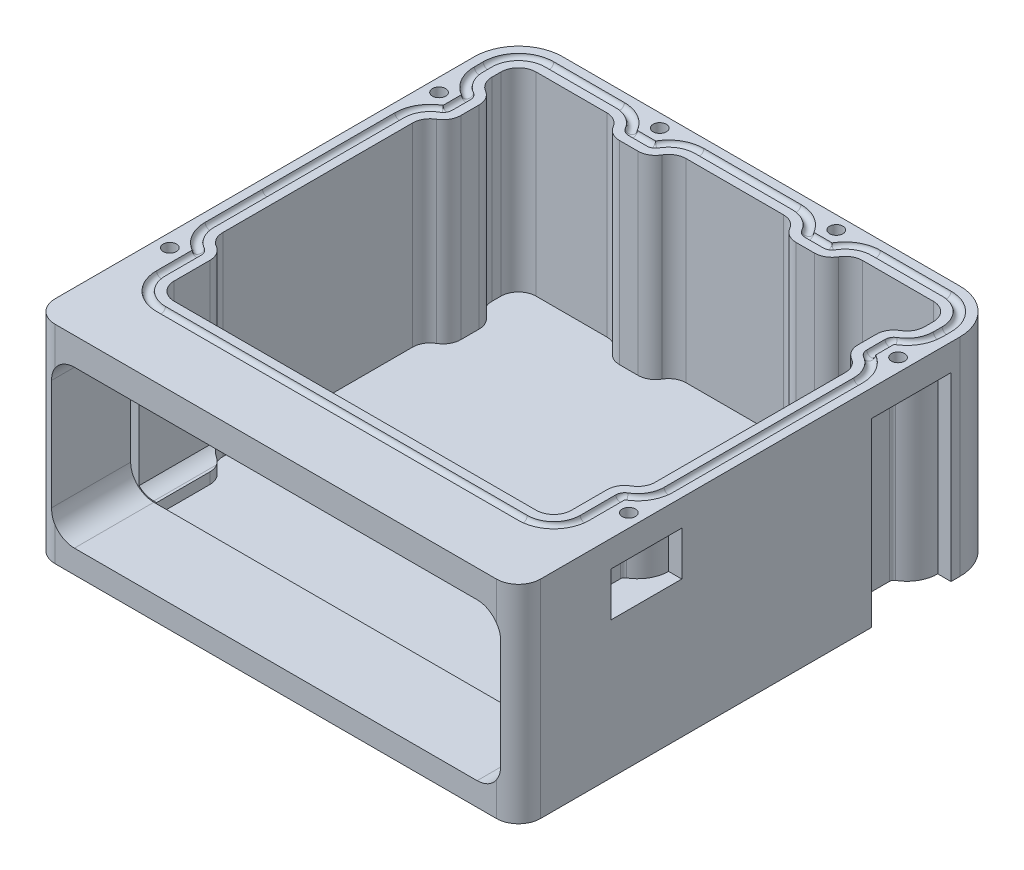
SolidWorks part; units mm, degrees
ref_plane "Front Plane" through (0, 0, 0) normal (0, 0, 1) x (1, 0, 0)
ref_plane "Top Plane" through (0, 0, 0) normal (0, 1, 0) x (1, 0, 0)
ref_plane "Right Plane" through (0, 0, 0) normal (1, 0, 0) x (0, 0, -1)
sketch "Sketch1" plane through (0, 0, 0) normal (0, 1, 0) x (1, 0, 0)
  line L1 (-45, 220) -> (45, 220)
  line L2 (-55, 210) -> (-55, 115)
  line L3 (-50, 110) -> (50, 110)
  line L4 (55, 210) -> (55, 115)
  arc A0 (45, 220) -> (55, 210) centre (45, 210) cw
  arc A1 (-45, 220) -> (-55, 210) centre (-45, 210) ccw
  arc A2 (50, 110) -> (55, 115) centre (50, 115) ccw
  arc A3 (-55, 115) -> (-50, 110) centre (-50, 115) ccw
  point P9 (-55, 220)
  point P12 (55, 110)
  point P15 (-55, 110)
  dimension "D5" = 10
  dimension "D6" = 5
  dimension "D1" = 110
  dimension "D2" = 110
  dimension "D3" = 55
  dimension "D4" = 110
extrude "Extrude-Thin1" add sketch "Sketch1" along normal blind 20 and the other way blind 27 thin thin type one direction reverse wall 6
sketch "Sketch2" plane through (0, -27, 0) normal (0, -1, 0) x (1, 0, 0)
  line L5 (-49, -116) -> (49, -116)
  line L6 (49, -116) -> (49, -210)
  line L7 (-49, -116) -> (-49, -210)
  line L8 (-45, -214) -> (45, -214)
  arc A6 (45, -214) -> (49, -210) centre (45, -210) ccw
  arc A7 (-49, -210) -> (-45, -214) centre (-45, -210) ccw
extrude "Boss-Extrude1" add sketch "Sketch2" against normal blind 3 contours A7 L8 A6 L6 L5 L7
sketch "Sketch4" plane through (0, 0, -116) normal (0, 0, -1) x (-1, 0, 0)
  line L0 (-45, 20) -> (-55, 20) construction
  line L1 (-52, 20) -> (52, 20)
  line L2 (-52, 20) -> (-52, -27)
  line L3 (-52, -27) -> (52, -27)
  line L4 (52, 20) -> (52, -27)
  line L5 (45, -27) -> (55, -27) construction
  line L6 (-55, -27) -> (-55, 20) construction
  line L7 (55, -27) -> (55, 20) construction
  dimension "D1" = 3
  dimension "D2" = 3
extrude "Boss-Extrude2" add sketch "Sketch4" along normal blind 12
sketch "Sketch3" plane through (0, 0, -110) normal (0, 0, 1) x (1, 0, 0)
  line L0 (-45.625, 13.75) -> (45.625, 13.75)
  line L5 (50.875, 8.5) -> (50.875, -16.5)
  line L6 (-45.625, 13.5) -> (45.625, 13.5)
  line L7 (-50.625, 8.5) -> (-50.625, -16.5)
  line L8 (-45.625, -21.5) -> (45.625, -21.5)
  line L9 (50.625, 8.5) -> (50.625, -16.5)
  line L10 (-45.625, -21.75) -> (45.625, -21.75)
  line L11 (-50.875, 8.5) -> (-50.875, -16.5)
  arc A1 (45.625, 13.75) -> (50.875, 8.5) centre (45.625, 8.5) cw
  arc A5 (-50.625, -16.5) -> (-45.625, -21.5) centre (-45.625, -16.5) ccw
  arc A6 (45.625, -21.5) -> (50.625, -16.5) centre (45.625, -16.5) ccw
  arc A7 (45.625, 13.5) -> (50.625, 8.5) centre (45.625, 8.5) cw
  arc A8 (-45.625, 13.5) -> (-50.625, 8.5) centre (-45.625, 8.5) ccw
  arc A9 (45.625, -21.75) -> (50.875, -16.5) centre (45.625, -16.5) ccw
  arc A10 (-50.875, -16.5) -> (-45.625, -21.75) centre (-45.625, -16.5) ccw
  arc A11 (-45.625, 13.75) -> (-50.875, 8.5) centre (-45.625, 8.5) ccw
  dimension "D1" = 5
  dimension "D5" = 13.5
  dimension "D2" = 50.625
  dimension "D3" = 101.25
  dimension "D4" = 35
  dimension "D6" = 0.25
extrude "Cut-Extrude1" cut sketch "Sketch3" against normal blind 18 contours L0 A1 L5 A9 L10 A10 L11 A11
sketch "Sketch5" plane through (0, -24, 0) normal (0, 1, 0) x (1, 0, 0)
  line L0 (0, 220) -> (0, 110) construction
  line L1 (45, 220) -> (-45, 220) construction
  line L2 (-50, 110) -> (50, 110) construction
  line L3 (45, 214) -> (-45, 214) construction
  line L4 (-15, 214) -> (-25, 214)
  line L5 (-15, 214) -> (-15, 210)
  line L6 (-15, 210) -> (-25, 210)
  line L7 (-25, 214) -> (-25, 210)
  line L8 (-45, 220) -> (-45, 188) construction
  line L9 (15, 214) -> (25, 214)
  line L10 (15, 214) -> (15, 210)
  line L11 (15, 210) -> (25, 210)
  line L12 (25, 214) -> (25, 210)
  line L13 (-45, 188) -> (-45, 210) construction
  line L14 (-45, 210) -> (-55, 210) construction
  line L15 (-55, 210) -> (55, 210) construction
  line L16 (45, 220) -> (45, 162.7672) construction
  line L17 (-49, 210) -> (-49, 128) construction
  line L18 (-45, 204) -> (-49, 204)
  line L19 (-45, 204) -> (-45, 194)
  line L20 (-45, 194) -> (-49, 194)
  line L21 (-49, 204) -> (-49, 194)
  line L22 (49, 128) -> (49, 210) construction
  line L23 (45, 204) -> (49, 204)
  line L24 (45, 204) -> (45, 194)
  line L25 (45, 194) -> (49, 194)
  line L26 (49, 204) -> (49, 194)
  line L27 (-49, 210) -> (-49, 128)
  line L28 (-49, 128) -> (-45, 128)
  line L29 (-49, 128) -> (-49, 143)
  line L30 (-49, 143) -> (-45, 143)
  line L31 (-45, 128) -> (-45, 143)
  line L32 (49, 128) -> (45, 128)
  line L33 (49, 128) -> (49, 143)
  line L34 (49, 143) -> (45, 143)
  line L35 (45, 128) -> (45, 143)
  line L36 (-45, 214) -> (45, 214)
  line L37 (49, 210) -> (49, 128)
  line M1 (-49, 210) -> (-49, 128)
  line M2 (-49, 128) -> (49, 128)
  line M6 (-49, 128) -> (49, 128)
  line M7 (49, 128) -> (49, 210)
  line M9 (45, 214) -> (-45, 214)
  dimension "D1" = 6
  dimension "D2" = 6
  dimension "D3" = 20
  dimension "D4" = 20
  dimension "D5" = 10
  dimension "D6" = 10
  dimension "D7" = 10
  dimension "D8" = 10
  dimension "D9" = 15
  dimension "D10" = 15
  dimension "D11" = 4
  dimension "D12" = 4
  dimension "D13" = 4
  dimension "D14" = 4
extrude "Boss-Extrude3" add sketch "Sketch5" along normal up to surface (44 mm away) contours L35 L34 M6 M7 | L24 L25 L23 M7 | L12 L10 L11 M9 | L7 L6 L5 M9 | L20 L19 L18 M1 | L31 L30 L27 M2 region at (-20, -24, -212) region at (20, -24, -212) region at (-47, -24, -199) region at (47, -24, -199) region at (47, -24, -135.5) region at (-47, -24, -135.5) up to face at (0, 20, -184.2761)
fillet "Fillet1" radius 4 10 edges at (49, -2, -194) (49, -2, -204) (25, -2, -214) (15, -2, -214) (-15, -2, -214) (-25, -2, -214) (-49, -2, -204) (-49, -2, -194) (49, -2, -143) (-49, -2, -143)
fillet "Fillet2" radius 4 12 edges at (-45, 16.875, -128) (45, 16.875, -128) (45, -2, -143) (-45, -2, -143) (45, -2, -204) (45, -2, -194) (25, -2, -210) (15, -2, -210) (-15, -2, -210) (-25, -2, -210) (-45, -2, -204) (-45, -2, -194)
ref_plane "Plane1" through (0, 0, -160) normal (0, 0, 1) x (1, 0, 0)
sketch "Sketch9" plane through (0, 20, 0) normal (0, 1, 0) x (1, 0, 0)
  line L329 (-17.9282, 213) -> (-22.0718, 213)
  line L330 (11, 217) -> (-11, 217)
  line L331 (22.0718, 213) -> (17.9282, 213)
  line L332 (45, 217) -> (29, 217)
  line L333 (52, 208) -> (52, 210)
  line L334 (48, 196.9282) -> (48, 201.0718)
  line L335 (52, 147) -> (52, 190)
  line L336 (48, 132) -> (48, 140.0718)
  line L337 (-41, 125) -> (41, 125)
  line L338 (-48, 140.0718) -> (-48, 132)
  line L339 (-52, 190) -> (-52, 147)
  line L340 (-48, 201.0718) -> (-48, 196.9282)
  line L341 (-52, 210) -> (-52, 208)
  line L342 (-29, 217) -> (-45, 217)
  line L343 (-17.9282, 213) -> (-22.0718, 213)
  line L344 (11, 217) -> (-11, 217)
  line L345 (22.0718, 213) -> (17.9282, 213)
  line L346 (45, 217) -> (29, 217)
  line L347 (52, 208) -> (52, 210)
  line L348 (48, 196.9282) -> (48, 201.0718)
  line L349 (52, 147) -> (52, 190)
  line L350 (48, 132) -> (48, 140.0718)
  line L351 (-41, 125) -> (41, 125)
  line L352 (-48, 140.0718) -> (-48, 132)
  line L353 (-52, 190) -> (-52, 147)
  line L354 (-48, 201.0718) -> (-48, 196.9282)
  line L355 (-52, 210) -> (-52, 208)
  line L356 (-29, 217) -> (-45, 217)
  arc A534 (-22.9378, 213.5) -> (-29, 217) centre (-29, 210) ccw
  arc A535 (-22.9378, 213.5) -> (-22.0718, 213) centre (-22.0718, 214) ccw
  arc A536 (-17.9282, 213) -> (-17.0622, 213.5) centre (-17.9282, 214) ccw
  arc A537 (-11, 217) -> (-17.0622, 213.5) centre (-11, 210) ccw
  arc A538 (17.0622, 213.5) -> (11, 217) centre (11, 210) ccw
  arc A539 (17.0622, 213.5) -> (17.9282, 213) centre (17.9282, 214) ccw
  arc A540 (22.0718, 213) -> (22.9378, 213.5) centre (22.0718, 214) ccw
  arc A541 (29, 217) -> (22.9378, 213.5) centre (29, 210) ccw
  arc A542 (52, 210) -> (45, 217) centre (45, 210) ccw
  arc A543 (48.5, 201.9378) -> (52, 208) centre (45, 208) ccw
  arc A544 (48.5, 201.9378) -> (48, 201.0718) centre (49, 201.0718) ccw
  arc A545 (48, 196.9282) -> (48.5, 196.0622) centre (49, 196.9282) ccw
  arc A546 (52, 190) -> (48.5, 196.0622) centre (45, 190) ccw
  arc A547 (48.5, 140.9378) -> (52, 147) centre (45, 147) ccw
  arc A548 (48.5, 140.9378) -> (48, 140.0718) centre (49, 140.0718) ccw
  arc A549 (41, 125) -> (48, 132) centre (41, 132) ccw
  arc A550 (-48, 132) -> (-41, 125) centre (-41, 132) ccw
  arc A551 (-48, 140.0718) -> (-48.5, 140.9378) centre (-49, 140.0718) ccw
  arc A552 (-52, 147) -> (-48.5, 140.9378) centre (-45, 147) ccw
  arc A553 (-48.5, 196.0622) -> (-52, 190) centre (-45, 190) ccw
  arc A554 (-48.5, 196.0622) -> (-48, 196.9282) centre (-49, 196.9282) ccw
  arc A555 (-48, 201.0718) -> (-48.5, 201.9378) centre (-49, 201.0718) ccw
  arc A556 (-52, 208) -> (-48.5, 201.9378) centre (-45, 208) ccw
  arc A557 (-45, 217) -> (-52, 210) centre (-45, 210) ccw
  arc A558 (-22.9378, 213.5) -> (-29, 217) centre (-29, 210) ccw
  arc A559 (-22.9378, 213.5) -> (-22.0718, 213) centre (-22.0718, 214) ccw
  arc A560 (-17.9282, 213) -> (-17.0622, 213.5) centre (-17.9282, 214) ccw
  arc A561 (-11, 217) -> (-17.0622, 213.5) centre (-11, 210) ccw
  arc A562 (17.0622, 213.5) -> (11, 217) centre (11, 210) ccw
  arc A563 (17.0622, 213.5) -> (17.9282, 213) centre (17.9282, 214) ccw
  arc A564 (22.0718, 213) -> (22.9378, 213.5) centre (22.0718, 214) ccw
  arc A565 (29, 217) -> (22.9378, 213.5) centre (29, 210) ccw
  arc A566 (52, 210) -> (45, 217) centre (45, 210) ccw
  arc A567 (48.5, 201.9378) -> (52, 208) centre (45, 208) ccw
  arc A568 (48.5, 201.9378) -> (48, 201.0718) centre (49, 201.0718) ccw
  arc A569 (48, 196.9282) -> (48.5, 196.0622) centre (49, 196.9282) ccw
  arc A570 (52, 190) -> (48.5, 196.0622) centre (45, 190) ccw
  arc A571 (48.5, 140.9378) -> (52, 147) centre (45, 147) ccw
  arc A572 (48.5, 140.9378) -> (48, 140.0718) centre (49, 140.0718) ccw
  arc A573 (41, 125) -> (48, 132) centre (41, 132) ccw
  arc A574 (-48, 132) -> (-41, 125) centre (-41, 132) ccw
  arc A575 (-48, 140.0718) -> (-48.5, 140.9378) centre (-49, 140.0718) ccw
  arc A576 (-52, 147) -> (-48.5, 140.9378) centre (-45, 147) ccw
  arc A577 (-48.5, 196.0622) -> (-52, 190) centre (-45, 190) ccw
  arc A578 (-48.5, 196.0622) -> (-48, 196.9282) centre (-49, 196.9282) ccw
  arc A579 (-48, 201.0718) -> (-48.5, 201.9378) centre (-49, 201.0718) ccw
  arc A580 (-52, 208) -> (-48.5, 201.9378) centre (-45, 208) ccw
  arc A581 (-45, 217) -> (-52, 210) centre (-45, 210) ccw
  dimension "D1" = 3
sketch "Sketch6" plane through (0, 0, -160) normal (0, 0, 1) x (1, 0, 0)
  line L0 (-45, 20) -> (-52, 20) construction
  line L1 (-50, 20) -> (-55, 20) construction
  circle A0 centre (-52, 20) radius 1
  dimension "D1" = 2
  dimension "D2" = 3
ref_plane "Plane2" through (0, 14, 0) normal (0, 1, 0) x (1, 0, 0)
sketch "Sketch10" plane through (0, 14, 0) normal (0, 1, 0) x (1, 0, 0)
  line L0 (-52, 147) -> (-55, 147)
  line L2 (52, 208) -> (55, 208)
  line L3 (-29, 220) -> (-29, 217)
  line L6 (-17.9282, 213) -> (-22.0718, 213)
  line L9 (-17.9282, 213) -> (-22.0718, 213)
  line L10 (-11, 217) -> (-11, 220)
  line L11 (-52, 208) -> (-55, 208)
  line L14 (-48, 201.0718) -> (-48, 196.9282)
  line L15 (-48, 201.0718) -> (-48, 196.9282)
  line L16 (-55, 190) -> (-52, 190)
  line L18 (48, 196.9282) -> (48, 201.0718)
  line L21 (48, 196.9282) -> (48, 201.0718)
  line L25 (-55, 210) -> (-55, 115) construction
  line L26 (-55, 208) -> (-55, 190)
  line L29 (45, 220) -> (-45, 220) construction
  line L30 (-29, 220) -> (-11, 220)
  line L33 (11, 220) -> (29, 220)
  line L36 (55, 115) -> (55, 210) construction
  line L37 (55, 208) -> (55, 190)
  line L40 (-55, 131) -> (-50.5, 131)
  line L41 (-48, 133.5) -> (-48, 140.0718)
  line L47 (52, 190) -> (55, 190)
  line L48 (-50, 110) -> (50, 110) construction
  line L49 (-55, 147) -> (-55, 131)
  line L50 (48, 140.0718) -> (48, 133.5)
  line L51 (50.5, 131) -> (55, 131)
  line L52 (-48, 140.0718) -> (-48, 132)
  line L55 (29, 217) -> (29, 220)
  line L56 (22.0718, 213) -> (17.9282, 213)
  line L57 (22.0718, 213) -> (17.9282, 213)
  line L58 (11, 220) -> (11, 217)
  line L59 (55, 131) -> (55, 147)
  line L60 (55, 147) -> (52, 147)
  line L61 (48, 132) -> (48, 140.0718)
  arc A0 (-50.5, 131) -> (-48, 133.5) centre (-50.5, 133.5) ccw
  arc A1 (48, 133.5) -> (50.5, 131) centre (50.5, 133.5) ccw
  arc A11 (52, 190) -> (48.5, 196.0622) centre (45, 190) ccw
  arc A12 (48, 196.9282) -> (48.5, 196.0622) centre (49, 196.9282) ccw
  arc A13 (-11, 217) -> (-17.0622, 213.5) centre (-11, 210) ccw
  arc A18 (-17.9282, 213) -> (-17.0622, 213.5) centre (-17.9282, 214) ccw
  arc A19 (-22.9378, 213.5) -> (-22.0718, 213) centre (-22.0718, 214) ccw
  arc A20 (48.5, 201.9378) -> (48, 201.0718) centre (49, 201.0718) ccw
  arc A21 (48.5, 201.9378) -> (52, 208) centre (45, 208) ccw
  arc A26 (-48.5, 196.0622) -> (-52, 190) centre (-45, 190) ccw
  arc A27 (-48.5, 196.0622) -> (-48, 196.9282) centre (-49, 196.9282) ccw
  arc A28 (-48, 201.0718) -> (-48.5, 201.9378) centre (-49, 201.0718) ccw
  arc A29 (-52, 208) -> (-48.5, 201.9378) centre (-45, 208) ccw
  arc A30 (-48.5, 196.0622) -> (-52, 190) centre (-45, 190) ccw
  arc A31 (-48.5, 196.0622) -> (-48, 196.9282) centre (-49, 196.9282) ccw
  arc A32 (-48, 201.0718) -> (-48.5, 201.9378) centre (-49, 201.0718) ccw
  arc A33 (-52, 208) -> (-48.5, 201.9378) centre (-45, 208) ccw
  arc A34 (52, 190) -> (48.5, 196.0622) centre (45, 190) ccw
  arc A35 (48, 196.9282) -> (48.5, 196.0622) centre (49, 196.9282) ccw
  arc A36 (48.5, 201.9378) -> (48, 201.0718) centre (49, 201.0718) ccw
  arc A37 (-22.9378, 213.5) -> (-29, 217) centre (-29, 210) ccw
  arc A38 (-11, 217) -> (-17.0622, 213.5) centre (-11, 210) ccw
  arc A39 (-17.9282, 213) -> (-17.0622, 213.5) centre (-17.9282, 214) ccw
  arc A40 (-22.9378, 213.5) -> (-22.0718, 213) centre (-22.0718, 214) ccw
  arc A41 (-22.9378, 213.5) -> (-29, 217) centre (-29, 210) ccw
  arc A42 (48.5, 201.9378) -> (52, 208) centre (45, 208) ccw
  arc A61 (-48, 140.0718) -> (-48.5, 140.9378) centre (-49, 140.0718) ccw
  arc A62 (-52, 147) -> (-48.5, 140.9378) centre (-45, 147) ccw
  arc A63 (-48, 140.0718) -> (-48.5, 140.9378) centre (-49, 140.0718) ccw
  arc A64 (-52, 147) -> (-48.5, 140.9378) centre (-45, 147) ccw
  arc A73 (48.5, 140.9378) -> (48, 140.0718) centre (49, 140.0718) ccw
  arc A78 (29, 217) -> (22.9378, 213.5) centre (29, 210) ccw
  arc A79 (22.0718, 213) -> (22.9378, 213.5) centre (22.0718, 214) ccw
  arc A80 (17.0622, 213.5) -> (17.9282, 213) centre (17.9282, 214) ccw
  arc A81 (17.0622, 213.5) -> (11, 217) centre (11, 210) ccw
  arc A82 (29, 217) -> (22.9378, 213.5) centre (29, 210) ccw
  arc A83 (22.0718, 213) -> (22.9378, 213.5) centre (22.0718, 214) ccw
  arc A84 (17.0622, 213.5) -> (17.9282, 213) centre (17.9282, 214) ccw
  arc A85 (17.0622, 213.5) -> (11, 217) centre (11, 210) ccw
  arc A90 (48.5, 140.9378) -> (52, 147) centre (45, 147) ccw
  arc A91 (48.5, 140.9378) -> (48, 140.0718) centre (49, 140.0718) ccw
  arc A92 (48.5, 140.9378) -> (52, 147) centre (45, 147) ccw
  dimension "D8" = 21
  dimension "D9" = 2.5
  dimension "D11" = 2.5
  dimension "D10" = 21
  dimension "D1" = 3
  dimension "D2" = 3
  dimension "D3" = 3
  dimension "D4" = 3
  dimension "D5" = 3
  dimension "D7" = 3
extrude "Cut-Extrude2" cut sketch "Sketch10" against normal blind 10
sketch "Sketch11" plane through (0, 14, 0) normal (0, -1, 0) x (1, 0, 0)
  line L0 (-55, -210) -> (-55, -115) construction
  line L1 (45, -220) -> (-45, -220) construction
  line L2 (55, -115) -> (55, -210) construction
  circle A0 centre (-52, -199) radius 1.5
  circle A1 centre (-20, -217.003) radius 1.5
  circle A2 centre (20, -217.003) radius 1.5
  circle A3 centre (52, -199) radius 1.5
  circle A4 centre (52, -138) radius 1.5
  circle A5 centre (-52, -138) radius 1.5
  point P7 (-49, -190)
  dimension "D3" = 3
  dimension "D4" = 3
  dimension "D5" = 3
  dimension "D6" = 3
  dimension "D8" = 2.997
  dimension "D9" = 9
  dimension "D10" = 2.997
  dimension "D11" = 9
  dimension "D12" = 3
  dimension "D13" = 3
  dimension "D14" = 3
  dimension "D17" = 3
  dimension "D18" = 3
  dimension "D2" = 9
  dimension "D7" = 9
  dimension "D15" = 9
  dimension "D16" = 9
  dimension "D1" = 3
extrude "Cut-Extrude3" cut sketch "Sketch11" against normal through all
sketch "Sketch15" plane through (0, 4, 0) normal (0, 1, 0) x (1, 0, 0)
  line L8 (-55, 208) -> (-55, 190)
  line L9 (-55, 190) -> (-52, 190)
  line L10 (-48, 196.9282) -> (-48, 201.0718)
  line L11 (-52, 208) -> (-55, 208)
  line L12 (-55, 208) -> (-55, 190)
  line L13 (-55, 190) -> (-52, 190)
  line L14 (-48, 196.9282) -> (-48, 201.0718)
  line L15 (-52, 208) -> (-55, 208)
  line L20 (-11, 220) -> (-29, 220)
  line L21 (-29, 220) -> (-29, 217)
  line L22 (-22.0718, 213) -> (-17.9282, 213)
  line L23 (-11, 217) -> (-11, 220)
  line L24 (-11, 220) -> (-29, 220)
  line L25 (-29, 220) -> (-29, 217)
  line L26 (-22.0718, 213) -> (-17.9282, 213)
  line L27 (-11, 217) -> (-11, 220)
  line L32 (29, 217) -> (29, 220)
  line L33 (29, 220) -> (11, 220)
  line L34 (11, 220) -> (11, 217)
  line L35 (17.9282, 213) -> (22.0718, 213)
  line L36 (29, 217) -> (29, 220)
  line L37 (29, 220) -> (11, 220)
  line L38 (11, 220) -> (11, 217)
  line L39 (17.9282, 213) -> (22.0718, 213)
  line L44 (55, 190) -> (55, 208)
  line L45 (55, 208) -> (52, 208)
  line L46 (48, 201.0718) -> (48, 196.9282)
  line L47 (52, 190) -> (55, 190)
  line L48 (55, 190) -> (55, 208)
  line L49 (55, 208) -> (52, 208)
  line L50 (48, 201.0718) -> (48, 196.9282)
  line L51 (52, 190) -> (55, 190)
  arc A8 (-48.5, 196.0622) -> (-52, 190) centre (-45, 190) ccw
  arc A9 (-48.5, 196.0622) -> (-48, 196.9282) centre (-49, 196.9282) ccw
  arc A10 (-48, 201.0718) -> (-48.5, 201.9378) centre (-49, 201.0718) ccw
  arc A11 (-52, 208) -> (-48.5, 201.9378) centre (-45, 208) ccw
  arc A12 (-48.5, 196.0622) -> (-52, 190) centre (-45, 190) ccw
  arc A13 (-48.5, 196.0622) -> (-48, 196.9282) centre (-49, 196.9282) ccw
  arc A14 (-48, 201.0718) -> (-48.5, 201.9378) centre (-49, 201.0718) ccw
  arc A15 (-52, 208) -> (-48.5, 201.9378) centre (-45, 208) ccw
  arc A20 (-22.9378, 213.5) -> (-29, 217) centre (-29, 210) ccw
  arc A21 (-22.9378, 213.5) -> (-22.0718, 213) centre (-22.0718, 214) ccw
  arc A22 (-17.9282, 213) -> (-17.0622, 213.5) centre (-17.9282, 214) ccw
  arc A23 (-11, 217) -> (-17.0622, 213.5) centre (-11, 210) ccw
  arc A24 (-22.9378, 213.5) -> (-29, 217) centre (-29, 210) ccw
  arc A25 (-22.9378, 213.5) -> (-22.0718, 213) centre (-22.0718, 214) ccw
  arc A26 (-17.9282, 213) -> (-17.0622, 213.5) centre (-17.9282, 214) ccw
  arc A27 (-11, 217) -> (-17.0622, 213.5) centre (-11, 210) ccw
  arc A32 (17.0622, 213.5) -> (11, 217) centre (11, 210) ccw
  arc A33 (17.0622, 213.5) -> (17.9282, 213) centre (17.9282, 214) ccw
  arc A34 (22.0718, 213) -> (22.9378, 213.5) centre (22.0718, 214) ccw
  arc A35 (29, 217) -> (22.9378, 213.5) centre (29, 210) ccw
  arc A36 (17.0622, 213.5) -> (11, 217) centre (11, 210) ccw
  arc A37 (17.0622, 213.5) -> (17.9282, 213) centre (17.9282, 214) ccw
  arc A38 (22.0718, 213) -> (22.9378, 213.5) centre (22.0718, 214) ccw
  arc A39 (29, 217) -> (22.9378, 213.5) centre (29, 210) ccw
  arc A44 (48.5, 201.9378) -> (52, 208) centre (45, 208) ccw
  arc A45 (48.5, 201.9378) -> (48, 201.0718) centre (49, 201.0718) ccw
  arc A46 (48, 196.9282) -> (48.5, 196.0622) centre (49, 196.9282) ccw
  arc A47 (52, 190) -> (48.5, 196.0622) centre (45, 190) ccw
  arc A48 (48.5, 201.9378) -> (52, 208) centre (45, 208) ccw
  arc A49 (48.5, 201.9378) -> (48, 201.0718) centre (49, 201.0718) ccw
  arc A50 (48, 196.9282) -> (48.5, 196.0622) centre (49, 196.9282) ccw
  arc A51 (52, 190) -> (48.5, 196.0622) centre (45, 190) ccw
  dimension "D1" = 0
  dimension "D2" = 0
  dimension "D3" = 0
  dimension "D4" = 0
extrude "Cut-Extrude6" cut sketch "Sketch15" against normal up to next
sketch "Sketch12" plane through (0, -27, 0) normal (0, -1, 0) x (1, 0, 0)
  line L0 (-50, -110) -> (50, -110) construction
  line L1 (-12, -110) -> (12, -110)
  line L2 (-12, -110) -> (-12, -232)
  line L4 (12, -110) -> (12, -232)
  line L5 (55, -115) -> (55, -190) construction
  line L7 (45, -220) -> (-45, -220) construction
  arc A0 (-12, -232) -> (12, -232) centre (0, -232) ccw
  circle A1 centre (0, -232) radius 2.75
  dimension "D5" = 24
  dimension "D3" = 5.5
  dimension "D4" = 12
  dimension "D1" = 24
  dimension "D2" = 43
extrude "Boss-Extrude4" add sketch "Sketch12" against normal blind 3
sketch "Sketch13" plane through (0, 0, -128) normal (0, 0, 1) x (1, 0, 0)
  line L0 (45.625, 13.5) -> (45, 13.5) construction
  line L1 (-45, 13.5) -> (-45, 0)
  line L3 (-55, -27) -> (-55, 20) construction
  line L4 (-45, 13.5) -> (45, 13.5)
  line L5 (45.625, 13.5) -> (-45.625, 13.5) construction
  line L6 (45, 13.5) -> (45, 0)
  line L9 (55, -27) -> (55, 20) construction
  line L10 (-45, 0) -> (-49, 0)
  line L13 (-45.625, -21.5) -> (45.625, -21.5)
  line L16 (49, 0) -> (45, 0)
  line L17 (-49, 0) -> (-49, -20.1891)
  line L18 (49, 0) -> (49, -20.1891)
  arc A0 (45.625, -21.5) -> (49, -20.1891) centre (45.625, -16.5) ccw
  arc A1 (-49, -20.1891) -> (-45.625, -21.5) centre (-45.625, -16.5) ccw
  point P0 (-45, 13.5)
  dimension "D3" = 5
  dimension "D10" = 3.375
  dimension "D1" = 10
  dimension "D2" = 10
  dimension "D4" = 6
  dimension "D5" = 6
  dimension "D6" = 91.25
  dimension "D7" = 13.5
  dimension "D8" = 13.5
  dimension "D9" = 35
extrude "Cut-Extrude4" cut sketch "Sketch13" against normal up to vertex (62 mm away) up to point (-49, -24, -190)
sweep "Cut-Sweep2" cut profiles "Sketch6" path "Sketch9"
ref_plane "Plane3" through (0, 20, 0) normal (0, 1, 0) x (1, 0, 0)
